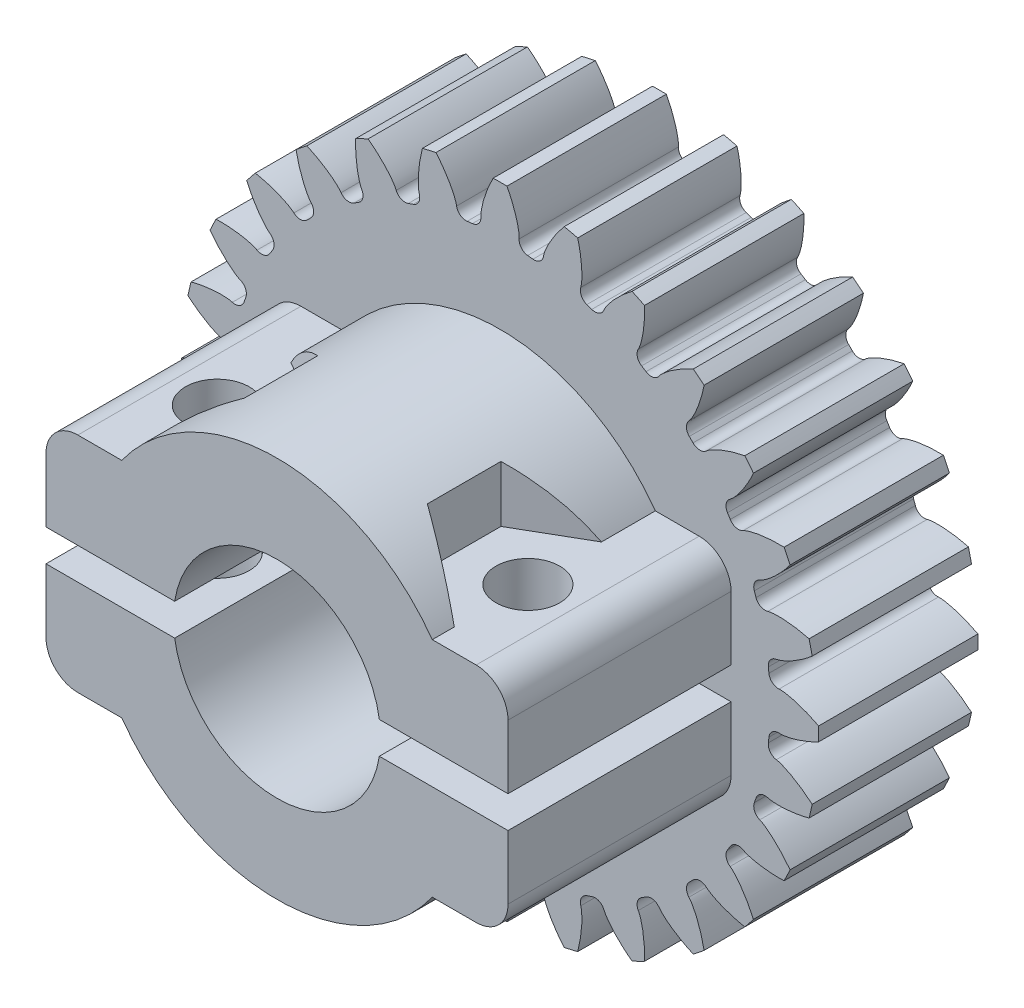
SolidWorks part; units mm, degrees
ref_plane "Front Plane" through (0, 0, 0) normal (0, 0, 1) x (1, 0, 0)
ref_plane "Top Plane" through (0, 0, 0) normal (0, 1, 0) x (1, 0, 0)
ref_plane "Right Plane" through (0, 0, 0) normal (1, 0, 0) x (0, 0, -1)
ref_plane "Plane1" through (0, 0, 3) normal (0, 0, 1) x (1, 0, 0)
sketch "Sketch1" plane through (0, 0, 3) normal (0, 0, 1) x (1, 0, 0)
  arc A0 (9.6987, -2.4361) -> (9.7952, -2.0133) centre (0, 0) ccw
  arc A1 (8.3795, -1.3179) -> (8.4627, -0.5798) centre (0, 0) ccw
  arc A2 (9.9976, -0.2169) -> (9.9976, 0.2169) centre (0, 0) ccw
  arc A3 (8.4627, 0.5798) -> (8.3795, 1.3179) centre (0, 0) ccw
  arc A4 (9.7952, 2.0133) -> (9.6987, 2.4361) centre (0, 0) ccw
  arc A5 (8.1215, 2.4484) -> (7.8762, 3.1495) centre (0, 0) ccw
  arc A6 (9.1017, 4.1424) -> (8.9135, 4.5332) centre (0, 0) ccw
  arc A7 (7.3731, 4.1942) -> (6.9779, 4.8231) centre (0, 0) ccw
  arc A8 (7.9517, 6.0639) -> (7.6813, 6.403) centre (0, 0) ccw
  arc A9 (6.2549, 5.7297) -> (5.7297, 6.2549) centre (0, 0) ccw
  arc A10 (6.403, 7.6813) -> (6.0639, 7.9517) centre (0, 0) ccw
  arc A11 (4.8231, 6.9779) -> (4.1942, 7.3731) centre (0, 0) ccw
  arc A12 (4.5332, 8.9135) -> (4.1424, 9.1017) centre (0, 0) ccw
  arc A13 (3.1495, 7.8762) -> (2.4484, 8.1215) centre (0, 0) ccw
  arc A14 (2.4361, 9.6987) -> (2.0133, 9.7952) centre (0, 0) ccw
  arc A15 (1.3179, 8.3795) -> (0.5798, 8.4627) centre (0, 0) ccw
  arc A16 (0.2169, 9.9976) -> (-0.2169, 9.9976) centre (0, 0) ccw
  arc A17 (-0.5798, 8.4627) -> (-1.3179, 8.3795) centre (0, 0) ccw
  arc A18 (-2.0133, 9.7952) -> (-2.4361, 9.6987) centre (0, 0) ccw
  arc A19 (-2.4484, 8.1215) -> (-3.1495, 7.8762) centre (0, 0) ccw
  arc A20 (-4.1424, 9.1017) -> (-4.5332, 8.9135) centre (0, 0) ccw
  arc A21 (-4.1942, 7.3731) -> (-4.8231, 6.9779) centre (0, 0) ccw
  arc A22 (-6.0639, 7.9517) -> (-6.403, 7.6813) centre (0, 0) ccw
  arc A23 (-5.7297, 6.2549) -> (-6.2549, 5.7297) centre (0, 0) ccw
  arc A24 (-7.6813, 6.403) -> (-7.9517, 6.0639) centre (0, 0) ccw
  arc A25 (-6.9779, 4.8231) -> (-7.3731, 4.1942) centre (0, 0) ccw
  arc A26 (-8.9135, 4.5332) -> (-9.1017, 4.1424) centre (0, 0) ccw
  arc A27 (-7.8762, 3.1495) -> (-8.1215, 2.4484) centre (0, 0) ccw
  arc A28 (-9.6987, 2.4361) -> (-9.7952, 2.0133) centre (0, 0) ccw
  arc A29 (-8.3795, 1.3179) -> (-8.4627, 0.5798) centre (0, 0) ccw
  arc A30 (-9.9976, 0.2169) -> (-9.9976, -0.2169) centre (0, 0) ccw
  arc A31 (-8.4627, -0.5798) -> (-8.3795, -1.3179) centre (0, 0) ccw
  arc A32 (-9.7952, -2.0133) -> (-9.6987, -2.4361) centre (0, 0) ccw
  arc A33 (-8.1215, -2.4484) -> (-7.8762, -3.1495) centre (0, 0) ccw
  arc A34 (-9.1017, -4.1424) -> (-8.9135, -4.5332) centre (0, 0) ccw
  arc A35 (-7.3731, -4.1942) -> (-6.9779, -4.8231) centre (0, 0) ccw
  arc A36 (-7.9517, -6.0639) -> (-7.6813, -6.403) centre (0, 0) ccw
  arc A37 (-6.2549, -5.7297) -> (-5.7297, -6.2549) centre (0, 0) ccw
  arc A38 (-6.403, -7.6813) -> (-6.0639, -7.9517) centre (0, 0) ccw
  arc A39 (-4.8231, -6.9779) -> (-4.1942, -7.3731) centre (0, 0) ccw
  arc A40 (-4.5332, -8.9135) -> (-4.1424, -9.1017) centre (0, 0) ccw
  arc A41 (-3.1495, -7.8762) -> (-2.4484, -8.1215) centre (0, 0) ccw
  arc A42 (-2.4361, -9.6987) -> (-2.0133, -9.7952) centre (0, 0) ccw
  arc A43 (-1.3179, -8.3795) -> (-0.5798, -8.4627) centre (0, 0) ccw
  arc A44 (-0.2169, -9.9976) -> (0.2169, -9.9976) centre (0, 0) ccw
  arc A45 (0.5798, -8.4627) -> (1.3179, -8.3795) centre (0, 0) ccw
  arc A46 (2.0133, -9.7952) -> (2.4361, -9.6987) centre (0, 0) ccw
  arc A47 (2.4484, -8.1215) -> (3.1495, -7.8762) centre (0, 0) ccw
  arc A48 (4.1424, -9.1017) -> (4.5332, -8.9135) centre (0, 0) ccw
  arc A49 (4.1942, -7.3731) -> (4.8231, -6.9779) centre (0, 0) ccw
  arc A50 (6.0639, -7.9517) -> (6.403, -7.6813) centre (0, 0) ccw
  arc A51 (5.7297, -6.2549) -> (6.2549, -5.7297) centre (0, 0) ccw
  arc A52 (7.6813, -6.403) -> (7.9517, -6.0639) centre (0, 0) ccw
  arc A53 (6.9779, -4.8231) -> (7.3731, -4.1942) centre (0, 0) ccw
  arc A54 (8.9135, -4.5332) -> (9.1017, -4.1424) centre (0, 0) ccw
  arc A55 (7.8762, -3.1495) -> (8.1215, -2.4484) centre (0, 0) ccw
  ellipse E0 centre (9.2657, -2.2723) end of major axis (10.2663, -2.1103) minor radius 0.2514 (8.4008, -2.5318) -> (9.6987, -2.4361) ccw
  ellipse E1 centre (9.3263, -1.932) end of major axis (10.1174, -2.4742) minor radius 0.222 (9.7952, -2.0133) -> (8.6673, -1.3639) ccw
  ellipse E2 centre (9.5391, -0.1536) end of major axis (10.4785, 0.2271) minor radius 0.2514 (8.7535, -0.599) -> (9.9976, -0.2169) ccw
  ellipse E3 centre (9.5224, 0.1918) end of major axis (10.4143, -0.1609) minor radius 0.222 (9.9976, 0.2169) -> (8.7535, 0.599) ccw
  ellipse E4 centre (9.3341, 1.9729) end of major axis (10.1652, 2.5531) minor radius 0.2514 (8.6673, 1.3639) -> (9.7952, 2.0133) ccw
  ellipse E5 centre (9.2409, 2.3059) end of major axis (10.189, 2.1606) minor radius 0.222 (9.6987, 2.4361) -> (8.4008, 2.5318) ccw
  ellipse E6 centre (8.661, 4.0005) end of major axis (7.9798, 3.25) minor radius 0.2514 (8.1465, 3.2583) -> (9.1017, 4.1424) ccw
  ellipse E7 centre (8.4961, 4.3044) end of major axis (9.4528, 4.3737) minor radius 0.222 (8.9135, 4.5332) -> (7.6268, 4.3377) ccw
  ellipse E8 centre (7.5537, 5.8275) end of major axis (8.0508, 6.7108) minor radius 0.2514 (7.2172, 4.9894) -> (7.9517, 6.0639) ccw
  ellipse E9 centre (7.3253, 6.087) end of major axis (8.2426, 6.3675) minor radius 0.222 (7.6813, 6.403) -> (6.4703, 5.926) ccw
  ellipse E10 centre (6.0676, 7.3622) end of major axis (5.7794, 6.3904) minor radius 0.2514 (5.926, 6.4703) -> (6.403, 7.6813) ccw
  ellipse E11 centre (5.7872, 7.5644) end of major axis (6.619, 8.042) minor radius 0.222 (6.0639, 7.9517) -> (4.9894, 7.2172) ccw
  ellipse E12 centre (4.2772, 8.5278) end of major axis (4.2125, 7.5162) minor radius 0.2514 (4.3377, 7.6268) -> (4.5332, 8.9135) ccw
  ellipse E13 centre (3.9588, 8.6625) end of major axis (4.6635, 9.3132) minor radius 0.222 (4.1424, 9.1017) -> (3.2583, 8.1465) ccw
  ellipse E14 centre (2.2723, 9.2657) end of major axis (2.4344, 8.2652) minor radius 0.2514 (2.5318, 8.4008) -> (2.4361, 9.6987) ccw
  ellipse E15 centre (1.932, 9.3263) end of major axis (1.3897, 8.5351) minor radius 0.222 (2.0133, 9.7952) -> (1.3639, 8.6673) ccw
  ellipse E16 centre (0.1536, 9.5391) end of major axis (0.5342, 8.5996) minor radius 0.2514 (0.599, 8.7535) -> (0.2169, 9.9976) ccw
  ellipse E17 centre (-0.1918, 9.5224) end of major axis (-0.5444, 8.6304) minor radius 0.222 (-0.2169, 9.9976) -> (-0.599, 8.7535) ccw
  ellipse E18 centre (-1.9729, 9.3341) end of major axis (-1.3928, 8.5029) minor radius 0.2514 (-1.3639, 8.6673) -> (-2.0133, 9.7952) ccw
  ellipse E19 centre (-2.3059, 9.2409) end of major axis (-2.4512, 8.2928) minor radius 0.222 (-2.4361, 9.6987) -> (-2.5318, 8.4008) ccw
  ellipse E20 centre (-4.0005, 8.661) end of major axis (-3.25, 7.9798) minor radius 0.2514 (-3.2583, 8.1465) -> (-4.1424, 9.1017) ccw
  ellipse E21 centre (-4.3044, 8.4961) end of major axis (-4.2351, 7.5395) minor radius 0.222 (-4.5332, 8.9135) -> (-4.3377, 7.6268) ccw
  ellipse E22 centre (-5.8275, 7.5537) end of major axis (-4.9442, 7.0565) minor radius 0.2514 (-4.9894, 7.2172) -> (-6.0639, 7.9517) ccw
  ellipse E23 centre (-6.087, 7.3253) end of major axis (-5.8066, 6.4081) minor radius 0.222 (-6.403, 7.6813) -> (-5.926, 6.4703) ccw
  ellipse E24 centre (-7.3622, 6.0676) end of major axis (-6.3904, 5.7794) minor radius 0.2514 (-6.4703, 5.926) -> (-7.6813, 6.403) ccw
  ellipse E25 centre (-7.5644, 5.7872) end of major axis (-8.042, 6.619) minor radius 0.222 (-7.9517, 6.0639) -> (-7.2172, 4.9894) ccw
  ellipse E26 centre (-8.5278, 4.2772) end of major axis (-9.5393, 4.3419) minor radius 0.2514 (-7.6268, 4.3377) -> (-8.9135, 4.5332) ccw
  ellipse E27 centre (-8.6625, 3.9588) end of major axis (-8.0119, 3.2541) minor radius 0.222 (-9.1017, 4.1424) -> (-8.1465, 3.2583) ccw
  ellipse E28 centre (-9.2657, 2.2723) end of major axis (-8.2652, 2.4344) minor radius 0.2514 (-8.4008, 2.5318) -> (-9.6987, 2.4361) ccw
  ellipse E29 centre (-9.3263, 1.932) end of major axis (-8.5351, 1.3897) minor radius 0.222 (-9.7952, 2.0133) -> (-8.6673, 1.3639) ccw
  ellipse E30 centre (-9.5391, 0.1536) end of major axis (-8.5996, 0.5342) minor radius 0.2514 (-8.7535, 0.599) -> (-9.9976, 0.2169) ccw
  ellipse E31 centre (-9.5224, -0.1918) end of major axis (-8.6304, -0.5444) minor radius 0.222 (-9.9976, -0.2169) -> (-8.7535, -0.599) ccw
  ellipse E32 centre (-9.3341, -1.9729) end of major axis (-8.5029, -1.3928) minor radius 0.2514 (-8.6673, -1.3639) -> (-9.7952, -2.0133) ccw
  ellipse E33 centre (-9.2409, -2.3059) end of major axis (-8.2928, -2.4512) minor radius 0.222 (-9.6987, -2.4361) -> (-8.4008, -2.5318) ccw
  ellipse E34 centre (-8.661, -4.0005) end of major axis (-9.3423, -4.751) minor radius 0.2514 (-8.1465, -3.2583) -> (-9.1017, -4.1424) ccw
  ellipse E35 centre (-8.4961, -4.3044) end of major axis (-7.5395, -4.2351) minor radius 0.222 (-8.9135, -4.5332) -> (-7.6268, -4.3377) ccw
  ellipse E36 centre (-7.5537, -5.8275) end of major axis (-8.0508, -6.7108) minor radius 0.2514 (-7.2172, -4.9894) -> (-7.9517, -6.0639) ccw
  ellipse E37 centre (-7.3253, -6.087) end of major axis (-6.4081, -5.8066) minor radius 0.222 (-7.6813, -6.403) -> (-6.4703, -5.926) ccw
  ellipse E38 centre (-6.0676, -7.3622) end of major axis (-6.3557, -8.334) minor radius 0.2514 (-5.926, -6.4703) -> (-6.403, -7.6813) ccw
  ellipse E39 centre (-5.7872, -7.5644) end of major axis (-4.9553, -7.0869) minor radius 0.222 (-6.0639, -7.9517) -> (-4.9894, -7.2172) ccw
  ellipse E40 centre (-4.2772, -8.5278) end of major axis (-4.3419, -9.5393) minor radius 0.2514 (-4.3377, -7.6268) -> (-4.5332, -8.9135) ccw
  ellipse E41 centre (-3.9588, -8.6625) end of major axis (-3.2541, -8.0119) minor radius 0.222 (-4.1424, -9.1017) -> (-3.2583, -8.1465) ccw
  ellipse E42 centre (-2.2723, -9.2657) end of major axis (-2.1103, -10.2663) minor radius 0.2514 (-2.5318, -8.4008) -> (-2.4361, -9.6987) ccw
  ellipse E43 centre (-1.932, -9.3263) end of major axis (-2.4742, -10.1174) minor radius 0.222 (-2.0133, -9.7952) -> (-1.3639, -8.6673) ccw
  ellipse E44 centre (-0.1536, -9.5391) end of major axis (0.2271, -10.4785) minor radius 0.2514 (-0.599, -8.7535) -> (-0.2169, -9.9976) ccw
  ellipse E45 centre (0.1918, -9.5224) end of major axis (-0.1609, -10.4143) minor radius 0.222 (0.2169, -9.9976) -> (0.599, -8.7535) ccw
  ellipse E46 centre (1.9729, -9.3341) end of major axis (2.5531, -10.1652) minor radius 0.2514 (1.3639, -8.6673) -> (2.0133, -9.7952) ccw
  ellipse E47 centre (2.3059, -9.2409) end of major axis (2.1606, -10.189) minor radius 0.222 (2.4361, -9.6987) -> (2.5318, -8.4008) ccw
  ellipse E48 centre (4.0005, -8.661) end of major axis (4.751, -9.3423) minor radius 0.2514 (3.2583, -8.1465) -> (4.1424, -9.1017) ccw
  ellipse E49 centre (4.3044, -8.4961) end of major axis (4.3737, -9.4528) minor radius 0.222 (4.5332, -8.9135) -> (4.3377, -7.6268) ccw
  ellipse E50 centre (5.8275, -7.5537) end of major axis (6.7108, -8.0508) minor radius 0.2514 (4.9894, -7.2172) -> (6.0639, -7.9517) ccw
  ellipse E51 centre (6.087, -7.3253) end of major axis (5.8066, -6.4081) minor radius 0.222 (6.403, -7.6813) -> (5.926, -6.4703) ccw
  ellipse E52 centre (7.3622, -6.0676) end of major axis (8.334, -6.3557) minor radius 0.2514 (6.4703, -5.926) -> (7.6813, -6.403) ccw
  ellipse E53 centre (7.5644, -5.7872) end of major axis (8.042, -6.619) minor radius 0.222 (7.9517, -6.0639) -> (7.2172, -4.9894) ccw
  ellipse E54 centre (8.5278, -4.2772) end of major axis (9.5393, -4.3419) minor radius 0.2514 (7.6268, -4.3377) -> (8.9135, -4.5332) ccw
  ellipse E55 centre (8.6625, -3.9588) end of major axis (9.3132, -4.6635) minor radius 0.222 (9.1017, -4.1424) -> (8.1465, -3.2583) ccw
  spline S0 degree 3 poles (8.6673, -1.3639) (8.5716, -1.3477) (8.4755, -1.3332) (8.3795, -1.3179) knots 0 0 0 0 1 1 1 1
  spline S1 degree 3 poles (8.7535, -0.599) (8.6566, -0.5935) (8.5596, -0.5862) (8.4627, -0.5798) knots 0 0 0 0 1 1 1 1
  spline S2 degree 3 poles (8.7535, 0.599) (8.6566, 0.5935) (8.5596, 0.5862) (8.4627, 0.5798) knots 0 0 0 0 1 1 1 1
  spline S3 degree 3 poles (8.6673, 1.3639) (8.5716, 1.3477) (8.4755, 1.3332) (8.3795, 1.3179) knots 0 0 0 0 1 1 1 1
  spline S4 degree 3 poles (8.4008, 2.5318) (8.3075, 2.5049) (8.2146, 2.4762) (8.1215, 2.4484) knots 0 0 0 0 1 1 1 1
  spline S5 degree 3 poles (8.1465, 3.2583) (8.0568, 3.2212) (7.9663, 3.1857) (7.8762, 3.1495) knots 0 0 0 0 1 1 1 1
  spline S6 degree 3 poles (7.6268, 4.3377) (7.5418, 4.2906) (7.4576, 4.242) (7.3731, 4.1942) knots 0 0 0 0 1 1 1 1
  spline S7 degree 3 poles (7.2172, 4.9894) (7.138, 4.9333) (7.0577, 4.8785) (6.9779, 4.8231) knots 0 0 0 0 1 1 1 1
  spline S8 degree 3 poles (6.4703, 5.926) (6.3979, 5.8613) (6.3267, 5.7951) (6.2549, 5.7297) knots 0 0 0 0 1 1 1 1
  spline S9 degree 3 poles (5.926, 6.4703) (5.8613, 6.3979) (5.7951, 6.3267) (5.7297, 6.2549) knots 0 0 0 0 1 1 1 1
  spline S10 degree 3 poles (4.9894, 7.2172) (4.9333, 7.138) (4.8785, 7.0577) (4.8231, 6.9779) knots 0 0 0 0 1 1 1 1
  spline S11 degree 3 poles (4.3377, 7.6268) (4.2906, 7.5418) (4.242, 7.4576) (4.1942, 7.3731) knots 0 0 0 0 1 1 1 1
  spline S12 degree 3 poles (3.2583, 8.1465) (3.2212, 8.0568) (3.1857, 7.9663) (3.1495, 7.8762) knots 0 0 0 0 1 1 1 1
  spline S13 degree 3 poles (2.5318, 8.4008) (2.5049, 8.3075) (2.4762, 8.2146) (2.4484, 8.1215) knots 0 0 0 0 1 1 1 1
  spline S14 degree 3 poles (1.3639, 8.6673) (1.3477, 8.5716) (1.3332, 8.4755) (1.3179, 8.3795) knots 0 0 0 0 1 1 1 1
  spline S15 degree 3 poles (0.599, 8.7535) (0.5935, 8.6566) (0.5862, 8.5596) (0.5798, 8.4627) knots 0 0 0 0 1 1 1 1
  spline S16 degree 3 poles (-0.599, 8.7535) (-0.5935, 8.6566) (-0.5862, 8.5596) (-0.5798, 8.4627) knots 0 0 0 0 1 1 1 1
  spline S17 degree 3 poles (-1.3639, 8.6673) (-1.3477, 8.5716) (-1.3332, 8.4755) (-1.3179, 8.3795) knots 0 0 0 0 1 1 1 1
  spline S18 degree 3 poles (-2.5318, 8.4008) (-2.5049, 8.3075) (-2.4762, 8.2146) (-2.4484, 8.1215) knots 0 0 0 0 1 1 1 1
  spline S19 degree 3 poles (-3.2583, 8.1465) (-3.2212, 8.0568) (-3.1857, 7.9663) (-3.1495, 7.8762) knots 0 0 0 0 1 1 1 1
  spline S20 degree 3 poles (-4.3377, 7.6268) (-4.2906, 7.5418) (-4.242, 7.4576) (-4.1942, 7.3731) knots 0 0 0 0 1 1 1 1
  spline S21 degree 3 poles (-4.9894, 7.2172) (-4.9333, 7.138) (-4.8785, 7.0577) (-4.8231, 6.9779) knots 0 0 0 0 1 1 1 1
  spline S22 degree 3 poles (-5.926, 6.4703) (-5.8613, 6.3979) (-5.7951, 6.3267) (-5.7297, 6.2549) knots 0 0 0 0 1 1 1 1
  spline S23 degree 3 poles (-6.4703, 5.926) (-6.3979, 5.8613) (-6.3267, 5.7951) (-6.2549, 5.7297) knots 0 0 0 0 1 1 1 1
  spline S24 degree 3 poles (-7.2172, 4.9894) (-7.138, 4.9333) (-7.0577, 4.8785) (-6.9779, 4.8231) knots 0 0 0 0 1 1 1 1
  spline S25 degree 3 poles (-7.6268, 4.3377) (-7.5418, 4.2906) (-7.4576, 4.242) (-7.3731, 4.1942) knots 0 0 0 0 1 1 1 1
  spline S26 degree 3 poles (-8.1465, 3.2583) (-8.0568, 3.2212) (-7.9663, 3.1857) (-7.8762, 3.1495) knots 0 0 0 0 1 1 1 1
  spline S27 degree 3 poles (-8.4008, 2.5318) (-8.3075, 2.5049) (-8.2146, 2.4762) (-8.1215, 2.4484) knots 0 0 0 0 1 1 1 1
  spline S28 degree 3 poles (-8.6673, 1.3639) (-8.5716, 1.3477) (-8.4755, 1.3332) (-8.3795, 1.3179) knots 0 0 0 0 1 1 1 1
  spline S29 degree 3 poles (-8.7535, 0.599) (-8.6566, 0.5935) (-8.5596, 0.5862) (-8.4627, 0.5798) knots 0 0 0 0 1 1 1 1
  spline S30 degree 3 poles (-8.7535, -0.599) (-8.6566, -0.5935) (-8.5596, -0.5862) (-8.4627, -0.5798) knots 0 0 0 0 1 1 1 1
  spline S31 degree 3 poles (-8.6673, -1.3639) (-8.5716, -1.3477) (-8.4755, -1.3332) (-8.3795, -1.3179) knots 0 0 0 0 1 1 1 1
  spline S32 degree 3 poles (-8.4008, -2.5318) (-8.3075, -2.5049) (-8.2146, -2.4762) (-8.1215, -2.4484) knots 0 0 0 0 1 1 1 1
  spline S33 degree 3 poles (-8.1465, -3.2583) (-8.0568, -3.2212) (-7.9663, -3.1857) (-7.8762, -3.1495) knots 0 0 0 0 1 1 1 1
  spline S34 degree 3 poles (-7.6268, -4.3377) (-7.5418, -4.2906) (-7.4576, -4.242) (-7.3731, -4.1942) knots 0 0 0 0 1 1 1 1
  spline S35 degree 3 poles (-7.2172, -4.9894) (-7.138, -4.9333) (-7.0577, -4.8785) (-6.9779, -4.8231) knots 0 0 0 0 1 1 1 1
  spline S36 degree 3 poles (-6.4703, -5.926) (-6.3979, -5.8613) (-6.3267, -5.7951) (-6.2549, -5.7297) knots 0 0 0 0 1 1 1 1
  spline S37 degree 3 poles (-5.926, -6.4703) (-5.8613, -6.3979) (-5.7951, -6.3267) (-5.7297, -6.2549) knots 0 0 0 0 1 1 1 1
  spline S38 degree 3 poles (-4.9894, -7.2172) (-4.9333, -7.138) (-4.8785, -7.0577) (-4.8231, -6.9779) knots 0 0 0 0 1 1 1 1
  spline S39 degree 3 poles (-4.3377, -7.6268) (-4.2906, -7.5418) (-4.242, -7.4576) (-4.1942, -7.3731) knots 0 0 0 0 1 1 1 1
  spline S40 degree 3 poles (-3.2583, -8.1465) (-3.2212, -8.0568) (-3.1857, -7.9663) (-3.1495, -7.8762) knots 0 0 0 0 1 1 1 1
  spline S41 degree 3 poles (-2.5318, -8.4008) (-2.5049, -8.3075) (-2.4762, -8.2146) (-2.4484, -8.1215) knots 0 0 0 0 1 1 1 1
  spline S42 degree 3 poles (-1.3639, -8.6673) (-1.3477, -8.5716) (-1.3332, -8.4755) (-1.3179, -8.3795) knots 0 0 0 0 1 1 1 1
  spline S43 degree 3 poles (-0.599, -8.7535) (-0.5935, -8.6566) (-0.5862, -8.5596) (-0.5798, -8.4627) knots 0 0 0 0 1 1 1 1
  spline S44 degree 3 poles (0.599, -8.7535) (0.5935, -8.6566) (0.5862, -8.5596) (0.5798, -8.4627) knots 0 0 0 0 1 1 1 1
  spline S45 degree 3 poles (1.3639, -8.6673) (1.3477, -8.5716) (1.3332, -8.4755) (1.3179, -8.3795) knots 0 0 0 0 1 1 1 1
  spline S46 degree 3 poles (2.5318, -8.4008) (2.5049, -8.3075) (2.4762, -8.2146) (2.4484, -8.1215) knots 0 0 0 0 1 1 1 1
  spline S47 degree 3 poles (3.2583, -8.1465) (3.2212, -8.0568) (3.1857, -7.9663) (3.1495, -7.8762) knots 0 0 0 0 1 1 1 1
  spline S48 degree 3 poles (4.3377, -7.6268) (4.2906, -7.5418) (4.242, -7.4576) (4.1942, -7.3731) knots 0 0 0 0 1 1 1 1
  spline S49 degree 3 poles (4.9894, -7.2172) (4.9333, -7.138) (4.8785, -7.0577) (4.8231, -6.9779) knots 0 0 0 0 1 1 1 1
  spline S50 degree 3 poles (5.926, -6.4703) (5.8613, -6.3979) (5.7951, -6.3267) (5.7297, -6.2549) knots 0 0 0 0 1 1 1 1
  spline S51 degree 3 poles (6.4703, -5.926) (6.3979, -5.8613) (6.3267, -5.7951) (6.2549, -5.7297) knots 0 0 0 0 1 1 1 1
  spline S52 degree 3 poles (7.2172, -4.9894) (7.138, -4.9333) (7.0577, -4.8785) (6.9779, -4.8231) knots 0 0 0 0 1 1 1 1
  spline S53 degree 3 poles (7.6268, -4.3377) (7.5418, -4.2906) (7.4576, -4.242) (7.3731, -4.1942) knots 0 0 0 0 1 1 1 1
  spline S54 degree 3 poles (8.1465, -3.2583) (8.0568, -3.2212) (7.9663, -3.1857) (7.8762, -3.1495) knots 0 0 0 0 1 1 1 1
  spline S55 degree 3 poles (8.4008, -2.5318) (8.3075, -2.5049) (8.2146, -2.4762) (8.1215, -2.4484) knots 0 0 0 0 1 1 1 1
  point P0 (9.2657, -2.2723)
  point P1 (10.2663, -2.1103)
  point P2 (9.3059, -2.5205)
  point P3 (8.4008, -2.5318)
  point P4 (9.6987, -2.4361)
  point P5 (9, -2.5579)
  point P6 (9.5315, -1.9868)
  point P16 (9.3263, -1.932)
  point P17 (10.1174, -2.4742)
  point P18 (9.2008, -2.115)
  point P19 (9.7952, -2.0133)
  point P20 (8.6673, -1.3639)
  point P21 (9.2186, -1.6003)
  point P22 (9.434, -2.2636)
  point P32 (9.5391, -0.1536)
  point P33 (10.4785, 0.2271)
  point P34 (9.6335, -0.3866)
  point P35 (8.7535, -0.599)
  point P36 (9.9976, -0.2169)
  point P37 (9.3435, -0.4911)
  point P38 (9.7346, 0.184)
  point P46 (9.5224, 0.1918)
  point P47 (10.4143, -0.1609)
  point P48 (9.4407, -0.0146)
  point P49 (9.9976, 0.2169)
  point P50 (8.7535, 0.599)
  point P51 (9.3435, 0.4911)
  point P52 (9.7012, -0.1076)
  point P62 (9.3341, 1.9729)
  point P63 (10.1652, 2.5531)
  point P64 (9.478, 1.7668)
  point P65 (8.6673, 1.3639)
  point P66 (9.7952, 2.0133)
  point P67 (9.2186, 1.6003)
  point P68 (9.4496, 2.3455)
  point P76 (9.2409, 2.3059)
  point P77 (10.189, 2.1606)
  point P78 (9.2073, 2.0865)
  point P79 (9.6987, 2.4361)
  point P80 (8.4008, 2.5318)
  point P81 (9, 2.5579)
  point P82 (9.4819, 2.0538)
  point P92 (8.661, 4.0005)
  point P93 (8.8472, 3.8315)
  point P94 (7.9798, 3.25)
  point P95 (8.1465, 3.2583)
  point P96 (9.1017, 4.1424)
  point P97 (8.6313, 3.6115)
  point P98 (8.6907, 4.3895)
  point P106 (8.4961, 4.3044)
  point P107 (9.4528, 4.3737)
  point P108 (8.5122, 4.083)
  point P109 (8.9135, 4.5332)
  point P110 (7.6268, 4.3377)
  point P111 (8.2052, 4.4965)
  point P112 (8.7871, 4.1123)
  point P122 (7.5537, 5.8275)
  point P123 (7.7728, 5.7041)
  point P124 (7.0565, 4.9442)
  point P125 (7.2172, 4.9894)
  point P126 (7.9517, 6.0639)
  point P127 (7.6113, 5.4416)
  point P128 (7.4961, 6.2133)
  point P136 (7.3253, 6.087)
  point P137 (8.2426, 6.3675)
  point P138 (7.3902, 5.8748)
  point P139 (7.6813, 6.403)
  point P140 (6.4703, 5.926)
  point P141 (6.9989, 6.2096)
  point P142 (7.6517, 5.9645)
  point P152 (6.0676, 7.3622)
  point P153 (6.3086, 7.2907)
  point P154 (5.7794, 6.3904)
  point P155 (5.926, 6.4703)
  point P156 (6.403, 7.6813)
  point P157 (6.2096, 6.9989)
  point P158 (5.9256, 7.7255)
  point P166 (5.7872, 7.5644)
  point P167 (6.619, 8.042)
  point P168 (5.8977, 7.3719)
  point P169 (6.0639, 7.9517)
  point P170 (4.9894, 7.2172)
  point P171 (5.4416, 7.6113)
  point P172 (6.1327, 7.5176)
  point P182 (4.2772, 8.5278)
  point P183 (4.5281, 8.5117)
  point P184 (4.2125, 7.5162)
  point P185 (4.3377, 7.6268)
  point P186 (4.5332, 8.9135)
  point P187 (4.4965, 8.2052)
  point P188 (4.0579, 8.8504)
  point P196 (3.9588, 8.6625)
  point P197 (4.6635, 9.3132)
  point P198 (4.1094, 8.4995)
  point P199 (4.1424, 9.1017)
  point P200 (3.2583, 8.1465)
  point P201 (3.6115, 8.6313)
  point P202 (4.3061, 8.6938)
  point P212 (2.2723, 9.2657)
  point P213 (2.5205, 9.3059)
  point P214 (2.4344, 8.2652)
  point P215 (2.5318, 8.4008)
  point P216 (2.4361, 9.6987)
  point P217 (2.5579, 9)
  point P218 (1.9868, 9.5315)
  point P226 (1.932, 9.3263)
  point P227 (2.115, 9.2008)
  point P228 (1.3897, 8.5351)
  point P229 (2.0133, 9.7952)
  point P230 (1.3639, 8.6673)
  point P231 (1.6003, 9.2186)
  point P232 (2.2636, 9.434)
  point P242 (0.1536, 9.5391)
  point P243 (0.3866, 9.6335)
  point P244 (0.5342, 8.5996)
  point P245 (0.599, 8.7535)
  point P246 (0.2169, 9.9976)
  point P247 (0.4911, 9.3435)
  point P248 (-0.184, 9.7346)
  point P256 (-0.1918, 9.5224)
  point P257 (0.0146, 9.4407)
  point P258 (-0.5444, 8.6304)
  point P259 (-0.2169, 9.9976)
  point P260 (-0.599, 8.7535)
  point P261 (-0.4911, 9.3435)
  point P262 (0.1076, 9.7012)
  point P272 (-1.9729, 9.3341)
  point P273 (-1.7668, 9.478)
  point P274 (-1.3928, 8.5029)
  point P275 (-1.3639, 8.6673)
  point P276 (-2.0133, 9.7952)
  point P277 (-1.6003, 9.2186)
  point P278 (-2.3455, 9.4496)
  point P286 (-2.3059, 9.2409)
  point P287 (-2.0865, 9.2073)
  point P288 (-2.4512, 8.2928)
  point P289 (-2.4361, 9.6987)
  point P290 (-2.5318, 8.4008)
  point P291 (-2.5579, 9)
  point P292 (-2.0538, 9.4819)
  point P302 (-4.0005, 8.661)
  point P303 (-3.25, 7.9798)
  point P304 (-4.1695, 8.4749)
  point P305 (-3.2583, 8.1465)
  point P306 (-4.1424, 9.1017)
  point P307 (-3.6115, 8.6313)
  point P308 (-4.3895, 8.6907)
  point P316 (-4.3044, 8.4961)
  point P317 (-4.083, 8.5122)
  point P318 (-4.2351, 7.5395)
  point P319 (-4.5332, 8.9135)
  point P320 (-4.3377, 7.6268)
  point P321 (-4.4965, 8.2052)
  point P322 (-4.1123, 8.7871)
  point P332 (-5.8275, 7.5537)
  point P333 (-4.9442, 7.0565)
  point P334 (-5.9508, 7.3346)
  point P335 (-4.9894, 7.2172)
  point P336 (-6.0639, 7.9517)
  point P337 (-5.4416, 7.6113)
  point P338 (-6.2133, 7.4961)
  point P346 (-6.087, 7.3253)
  point P347 (-5.8748, 7.3902)
  point P348 (-5.8066, 6.4081)
  point P349 (-6.403, 7.6813)
  point P350 (-5.926, 6.4703)
  point P351 (-6.2096, 6.9989)
  point P352 (-5.9645, 7.6517)
  point P362 (-7.3622, 6.0676)
  point P363 (-6.3904, 5.7794)
  point P364 (-7.4337, 5.8265)
  point P365 (-6.4703, 5.926)
  point P366 (-7.6813, 6.403)
  point P367 (-6.9989, 6.2096)
  point P368 (-7.7255, 5.9256)
  point P376 (-7.5644, 5.7872)
  point P377 (-7.3719, 5.8977)
  point P378 (-7.0869, 4.9553)
  point P379 (-7.9517, 6.0639)
  point P380 (-7.2172, 4.9894)
  point P381 (-7.6113, 5.4416)
  point P382 (-7.5176, 6.1327)
  point P392 (-8.5278, 4.2772)
  point P393 (-7.5162, 4.2125)
  point P394 (-8.5438, 4.0263)
  point P395 (-7.6268, 4.3377)
  point P396 (-8.9135, 4.5332)
  point P397 (-8.2052, 4.4965)
  point P398 (-8.8504, 4.0579)
  point P406 (-8.6625, 3.9588)
  point P407 (-8.4995, 4.1094)
  point P408 (-8.0119, 3.2541)
  point P409 (-9.1017, 4.1424)
  point P410 (-8.1465, 3.2583)
  point P411 (-8.6313, 3.6115)
  point P412 (-8.6938, 4.3061)
  point P422 (-9.2657, 2.2723)
  point P423 (-8.2652, 2.4344)
  point P424 (-9.2255, 2.0242)
  point P425 (-8.4008, 2.5318)
  point P426 (-9.6987, 2.4361)
  point P427 (-9, 2.5579)
  point P428 (-9.5315, 1.9868)
  point P436 (-9.3263, 1.932)
  point P437 (-8.5351, 1.3897)
  point P438 (-9.4518, 1.7489)
  point P439 (-9.7952, 2.0133)
  point P440 (-8.6673, 1.3639)
  point P441 (-9.2186, 1.6003)
  point P442 (-9.434, 2.2636)
  point P452 (-9.5391, 0.1536)
  point P453 (-8.5996, 0.5342)
  point P454 (-9.4447, -0.0795)
  point P455 (-8.7535, 0.599)
  point P456 (-9.9976, 0.2169)
  point P457 (-9.3435, 0.4911)
  point P458 (-9.7346, -0.184)
  point P466 (-9.5224, -0.1918)
  point P467 (-8.6304, -0.5444)
  point P468 (-9.604, -0.3982)
  point P469 (-9.9976, -0.2169)
  point P470 (-8.7535, -0.599)
  point P471 (-9.3435, -0.4911)
  point P472 (-9.7012, 0.1076)
  point P482 (-9.3341, -1.9729)
  point P483 (-8.5029, -1.3928)
  point P484 (-9.1902, -2.1791)
  point P485 (-8.6673, -1.3639)
  point P486 (-9.7952, -2.0133)
  point P487 (-9.2186, -1.6003)
  point P488 (-9.4496, -2.3455)
  point P496 (-9.2409, -2.3059)
  point P497 (-8.2928, -2.4512)
  point P498 (-9.2746, -2.5253)
  point P499 (-9.6987, -2.4361)
  point P500 (-8.4008, -2.5318)
  point P501 (-9, -2.5579)
  point P502 (-9.4819, -2.0538)
  point P512 (-8.661, -4.0005)
  point P513 (-8.4749, -4.1695)
  point P514 (-9.3423, -4.751)
  point P515 (-8.1465, -3.2583)
  point P516 (-9.1017, -4.1424)
  point P517 (-8.6313, -3.6115)
  point P518 (-8.6907, -4.3895)
  point P526 (-8.4961, -4.3044)
  point P527 (-7.5395, -4.2351)
  point P528 (-8.4801, -4.5258)
  point P529 (-8.9135, -4.5332)
  point P530 (-7.6268, -4.3377)
  point P531 (-8.2052, -4.4965)
  point P532 (-8.7871, -4.1123)
  point P542 (-7.5537, -5.8275)
  point P543 (-7.3346, -5.9508)
  point P544 (-8.0508, -6.7108)
  point P545 (-7.2172, -4.9894)
  point P546 (-7.9517, -6.0639)
  point P547 (-7.6113, -5.4416)
  point P548 (-7.4961, -6.2133)
  point P556 (-7.3253, -6.087)
  point P557 (-6.4081, -5.8066)
  point P558 (-7.2604, -6.2993)
  point P559 (-7.6813, -6.403)
  point P560 (-6.4703, -5.926)
  point P561 (-6.9989, -6.2096)
  point P562 (-7.6517, -5.9645)
  point P572 (-6.0676, -7.3622)
  point P573 (-5.8265, -7.4337)
  point P574 (-6.3557, -8.334)
  point P575 (-5.926, -6.4703)
  point P576 (-6.403, -7.6813)
  point P577 (-6.2096, -6.9989)
  point P578 (-5.9256, -7.7255)
  point P586 (-5.7872, -7.5644)
  point P587 (-4.9553, -7.0869)
  point P588 (-5.6767, -7.7569)
  point P589 (-6.0639, -7.9517)
  point P590 (-4.9894, -7.2172)
  point P591 (-5.4416, -7.6113)
  point P592 (-6.1327, -7.5176)
  point P602 (-4.2772, -8.5278)
  point P603 (-4.0263, -8.5438)
  point P604 (-4.3419, -9.5393)
  point P605 (-4.3377, -7.6268)
  point P606 (-4.5332, -8.9135)
  point P607 (-4.4965, -8.2052)
  point P608 (-4.0579, -8.8504)
  point P616 (-3.9588, -8.6625)
  point P617 (-3.2541, -8.0119)
  point P618 (-3.8082, -8.8256)
  point P619 (-4.1424, -9.1017)
  point P620 (-3.2583, -8.1465)
  point P621 (-3.6115, -8.6313)
  point P622 (-4.3061, -8.6938)
  point P632 (-2.2723, -9.2657)
  point P633 (-2.0242, -9.2255)
  point P634 (-2.1103, -10.2663)
  point P635 (-2.5318, -8.4008)
  point P636 (-2.4361, -9.6987)
  point P637 (-2.5579, -9)
  point P638 (-1.9868, -9.5315)
  point P646 (-1.932, -9.3263)
  point P647 (-1.7489, -9.4518)
  point P648 (-2.4742, -10.1174)
  point P649 (-2.0133, -9.7952)
  point P650 (-1.3639, -8.6673)
  point P651 (-1.6003, -9.2186)
  point P652 (-2.2636, -9.434)
  point P662 (-0.1536, -9.5391)
  point P663 (0.0795, -9.4447)
  point P664 (0.2271, -10.4785)
  point P665 (-0.599, -8.7535)
  point P666 (-0.2169, -9.9976)
  point P667 (-0.4911, -9.3435)
  point P668 (0.184, -9.7346)
  point P676 (0.1918, -9.5224)
  point P677 (0.3982, -9.604)
  point P678 (-0.1609, -10.4143)
  point P679 (0.2169, -9.9976)
  point P680 (0.599, -8.7535)
  point P681 (0.4911, -9.3435)
  point P682 (-0.1076, -9.7012)
  point P692 (1.9729, -9.3341)
  point P693 (2.1791, -9.1902)
  point P694 (2.5531, -10.1652)
  point P695 (1.3639, -8.6673)
  point P696 (2.0133, -9.7952)
  point P697 (1.6003, -9.2186)
  point P698 (2.3455, -9.4496)
  point P706 (2.3059, -9.2409)
  point P707 (2.5253, -9.2746)
  point P708 (2.1606, -10.189)
  point P709 (2.4361, -9.6987)
  point P710 (2.5318, -8.4008)
  point P711 (2.5579, -9)
  point P712 (2.0538, -9.4819)
  point P722 (4.0005, -8.661)
  point P723 (4.751, -9.3423)
  point P724 (3.8315, -8.8472)
  point P725 (3.2583, -8.1465)
  point P726 (4.1424, -9.1017)
  point P727 (3.6115, -8.6313)
  point P728 (4.3895, -8.6907)
  point P736 (4.3044, -8.4961)
  point P737 (4.5258, -8.4801)
  point P738 (4.3737, -9.4528)
  point P739 (4.5332, -8.9135)
  point P740 (4.3377, -7.6268)
  point P741 (4.4965, -8.2052)
  point P742 (4.1123, -8.7871)
  point P752 (5.8275, -7.5537)
  point P753 (6.7108, -8.0508)
  point P754 (5.7041, -7.7728)
  point P755 (4.9894, -7.2172)
  point P756 (6.0639, -7.9517)
  point P757 (5.4416, -7.6113)
  point P758 (6.2133, -7.4961)
  point P766 (6.087, -7.3253)
  point P767 (6.2993, -7.2604)
  point P768 (6.3675, -8.2426)
  point P769 (6.403, -7.6813)
  point P770 (5.926, -6.4703)
  point P771 (6.2096, -6.9989)
  point P772 (5.9645, -7.6517)
  point P782 (7.3622, -6.0676)
  point P783 (8.334, -6.3557)
  point P784 (7.2907, -6.3086)
  point P785 (6.4703, -5.926)
  point P786 (7.6813, -6.403)
  point P787 (6.9989, -6.2096)
  point P788 (7.7255, -5.9256)
  point P796 (7.5644, -5.7872)
  point P797 (7.7569, -5.6767)
  point P798 (8.042, -6.619)
  point P799 (7.9517, -6.0639)
  point P800 (7.2172, -4.9894)
  point P801 (7.6113, -5.4416)
  point P802 (7.5176, -6.1327)
  point P812 (8.5278, -4.2772)
  point P813 (9.5393, -4.3419)
  point P814 (8.5117, -4.5281)
  point P815 (7.6268, -4.3377)
  point P816 (8.9135, -4.5332)
  point P817 (8.2052, -4.4965)
  point P818 (8.8504, -4.0579)
  point P826 (8.6625, -3.9588)
  point P827 (8.8256, -3.8082)
  point P828 (9.3132, -4.6635)
  point P829 (9.1017, -4.1424)
  point P830 (8.1465, -3.2583)
  point P831 (8.6313, -3.6115)
  point P832 (8.6938, -4.3061)
extrude "Boss-Extrude1" add sketch "Sketch1" against normal blind 5
hole_wizard "Ø6.0 (6) Diameter Hole1" positions "Sketch3" profile "Sketch2" hole size "Ø6.0" standard "ANSI Metric" end condition through all
sketch "Sketch3" plane through (0, 0, 3) normal (0, 0, 1) x (1, 0, 0)
  point P0 (0, 0)
sketch "Sketch2" plane through (0, 0, 3) normal (1, 0, 0) x (0, -1, 0)
  line L0 (0, 0) -> (0, 5)
  line L1 (0, 5) -> (3, 5)
  line L2 (3, 5) -> (3, 0)
  line L5 (3, 0) -> (0, 0)
  line L11 (0, -6.35) -> (0, 107.95) construction
  dimension "Thru Hole Dia." = 6
  dimension "Thru Hole Depth" = 5
fillet "Fillet1" radius 0.3 56 edges at (-7.3731, 4.1942, 0.5) (5.7297, 6.2549, 0.5) (-1.3179, 8.3795, 0.5) (8.1215, -2.4484, 0.5) (8.4627, -0.5798, 0.5) (7.8762, -3.1495, 0.5) (-4.8231, 6.9779, 0.5) (7.3731, -4.1942, 0.5) (2.4484, 8.1215, 0.5) (6.9779, -4.8231, 0.5) (7.8762, 3.1495, 0.5) (6.2549, -5.7297, 0.5) (-8.1215, 2.4484, 0.5) (5.7297, -6.2549, 0.5) (-6.2549, 5.7297, 0.5) (4.8231, -6.9779, 0.5) (-3.1495, 7.8762, 0.5) (4.1942, -7.3731, 0.5) (0.5798, 8.4627, 0.5) (3.1495, -7.8762, 0.5) (4.1942, 7.3731, 0.5) (2.4484, -8.1215, 0.5) (6.9779, 4.8231, 0.5) (1.3179, -8.3795, 0.5) (8.3795, 1.3179, 0.5) (0.5798, -8.4627, 0.5) (-8.3795, 1.3179, 0.5) (-0.5798, -8.4627, 0.5) (-7.8762, 3.1495, 0.5) (-1.3179, -8.3795, 0.5) (-6.9779, 4.8231, 0.5) (-2.4484, -8.1215, 0.5) (-5.7297, 6.2549, 0.5) (-3.1495, -7.8762, 0.5) (-4.1942, 7.3731, 0.5) (-4.1942, -7.3731, 0.5) (-2.4484, 8.1215, 0.5) (-4.8231, -6.9779, 0.5) (-0.5798, 8.4627, 0.5) (-5.7297, -6.2549, 0.5) (1.3179, 8.3795, 0.5) (-6.2549, -5.7297, 0.5) (3.1495, 7.8762, 0.5) (-6.9779, -4.8231, 0.5) (4.8231, 6.9779, 0.5) (-7.3731, -4.1942, 0.5) (6.2549, 5.7297, 0.5) (-7.8762, -3.1495, 0.5) (7.3731, 4.1942, 0.5) (-8.1215, -2.4484, 0.5) (8.1215, 2.4484, 0.5) (-8.3795, -1.3179, 0.5) (8.4627, 0.5798, 0.5) (-8.4627, -0.5798, 0.5) (8.3795, -1.3179, 0.5) (-8.4627, 0.5798, 0.5) tangent propagation no
sketch "Sketch4" plane through (0, 0, 3) normal (0, 0, 1) x (1, 0, 0)
  circle A0 centre (0, 0) radius 3
  circle A1 centre (0, 0) radius 6
  dimension "D1" = 6
  dimension "D2" = 12
extrude "Boss-Extrude2" add sketch "Sketch4" along normal blind 7
sketch "Sketch5" plane through (0, 0, 3) normal (0, 0, 1) x (1, 0, 0)
  circle A0 centre (0, 0) radius 1
  circle A1 centre (0, 0) radius 3.25
  dimension "D1" = 6.5
extrude "Cut-Extrude1" cut sketch "Sketch5" against normal blind 11.5 and the other way blind 10
sketch "Sketch6" plane through (0, 0, 10) normal (0, 0, 1) x (1, 0, 0)
  line L0 (3.25, 3.5) -> (-3.25, -3.5) construction
  line L1 (-3.25, -3.5) -> (-6.25, -3.5)
  line L2 (-3.25, -3.5) -> (-3.25, 3.5)
  line L3 (-3.25, 3.5) -> (-6.25, 3.5)
  line L4 (-7.25, -2.5) -> (-7.25, 2.5)
  line L5 (3.25, -3.5) -> (6.25, -3.5)
  line L6 (3.25, -3.5) -> (3.25, 3.5)
  line L7 (3.25, 3.5) -> (6.25, 3.5)
  line L8 (7.25, -2.5) -> (7.25, 2.5)
  arc A1 (-6.25, -3.5) -> (-7.25, -2.5) centre (-6.25, -2.5) cw
  arc A2 (-6.25, 3.5) -> (-7.25, 2.5) centre (-6.25, 2.5) ccw
  arc A3 (7.25, -2.5) -> (6.25, -3.5) centre (6.25, -2.5) cw
  arc A4 (6.25, 3.5) -> (7.25, 2.5) centre (6.25, 2.5) cw
  circle A5 centre (0, 0) radius 3.25 construction
  point P8 (-3.25, 0)
  point P10 (0, 0)
  point P22 (7.25, -3.5)
  point P25 (7.25, 3.5)
  dimension "D3" = 1
  dimension "D1" = 7
  dimension "D2" = 4
extrude "Boss-Extrude3" add sketch "Sketch6" against normal blind 7
sketch "Sketch7" plane through (0, 0, 10) normal (0, 0, 1) x (1, 0, 0)
  line L0 (7.25, -2.5) -> (7.25, 2.5) construction
  line L1 (7.25, 0.5) -> (-7.25, 0.5)
  line L2 (7.25, 0.5) -> (7.25, -0.5)
  line L3 (7.25, -0.5) -> (-7.25, -0.5)
  line L4 (-7.25, 0.5) -> (-7.25, -0.5)
  line L5 (-7.25, 2.5) -> (-7.25, -2.5) construction
  point P10 (7.25, 0)
  point P11 (7.25, 0)
  dimension "D1" = 1
extrude "Cut-Extrude2" cut sketch "Sketch7" against normal up to surface (7 mm away) up to face at (0, 0, 3)
sketch "Sketch8" plane through (0, -3.5, 0) normal (0, -1, 0) x (1, 0, 0)
  line L0 (4.8734, 7) -> (-4.8734, 7) construction
  line L1 (4.8734, 10) -> (6.25, 10) construction
  line L2 (-4.8734, 10) -> (-4.8734, 3) construction
  circle A0 centre (4.8734, 7) radius 1
  circle A1 centre (-4.8734, 7) radius 1
  point P4 (0, 7)
  dimension "D1" = 2
  dimension "D2" = 3
extrude "Cut-Extrude3" cut sketch "Sketch8" against normal blind 7
sketch "Sketch9" plane through (0, -3.5, 0) normal (0, -1, 0) x (1, 0, 0)
  circle A0 centre (4.8734, 7) radius 2
  circle A1 centre (-4.8734, 7) radius 2
  dimension "D1" = 4
extrude "Cut-Extrude4" cut sketch "Sketch9" along normal blind 7
sketch "Sketch10" plane through (0, 3.5, 0) normal (0, 1, 0) x (1, 0, 0)
  line L1 (-4.8734, -4.6906) -> (-6.8734, -5.8453)
  line L2 (-6.8734, -5.8453) -> (-6.8734, -8.1547)
  line L3 (-6.8734, -8.1547) -> (-4.8734, -9.3094)
  line L4 (-4.8734, -9.3094) -> (-2.8734, -8.1547)
  line L5 (-2.8734, -8.1547) -> (-2.8734, -5.8453)
  line L6 (-2.8734, -5.8453) -> (-4.8734, -4.6906)
  line L7 (4.8734, -4.6906) -> (2.8734, -5.8453)
  line L8 (2.8734, -5.8453) -> (2.8734, -8.1547)
  line L9 (2.8734, -8.1547) -> (4.8734, -9.3094)
  line L10 (4.8734, -9.3094) -> (6.8734, -8.1547)
  line L11 (6.8734, -8.1547) -> (6.8734, -5.8453)
  line L12 (6.8734, -5.8453) -> (4.8734, -4.6906)
  line L13 (-6.25, -3) -> (-6.25, -10) construction
  circle A0 centre (-4.8734, -7) radius 2 construction
  circle A1 centre (4.8734, -7) radius 2 construction
  arc A2 (-4.8734, -6) -> (-4.8734, -8) centre (-4.8734, -7) ccw construction
  dimension "D1" = 4
extrude "Cut-Extrude5" cut sketch "Sketch10" along normal blind 7
